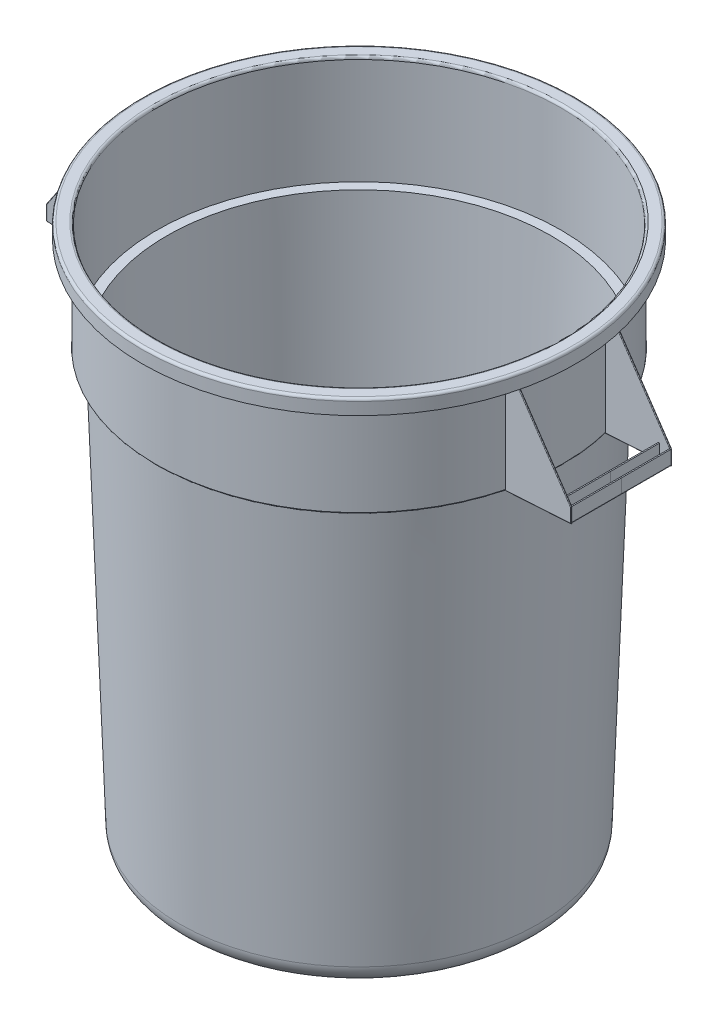
SolidWorks part; units mm, degrees
ref_plane "Front Plane" through (0, 0, 0) normal (0, 0, 1) x (1, 0, 0)
ref_plane "Top Plane" through (0, 0, 0) normal (0, 1, 0) x (1, 0, 0)
ref_plane "Center Plane" through (0, 0, 0) normal (1, 0, 0) x (0, 0, -1)
sketch "Sketch1" plane through (0, 0, 0) normal (0, 0, 1) x (1, 0, 0)
  line L0 (-158.75, 0) -> (-228.6, 0)
  line L1 (-228.6, 0) -> (-247.892, 552.45)
  line L2 (-260.592, 692.15) -> (-279.642, 692.15)
  line L3 (-279.642, 692.15) -> (-279.642, 673.1)
  line L4 (-158.75, 0) -> (-158.75, 34.925)
  line L5 (0, 0) -> (0, 802.8221) construction
  line L6 (-158.75, 34.925) -> (0, 34.925)
  line L7 (-247.892, 552.45) -> (-260.592, 552.45)
  line L8 (-260.592, 552.45) -> (-260.592, 692.15)
  line L9 (-157.1625, 33.3375) -> (0, 33.3375)
  line L10 (-157.1625, -1.5875) -> (-157.1625, 33.3375)
  line L11 (-157.1625, -1.5875) -> (-230.133, -1.5875)
  line L12 (-230.133, -1.5875) -> (-249.425, 550.8625)
  line L13 (-249.425, 550.8625) -> (-262.1795, 550.8625)
  line L14 (-262.1795, 550.8625) -> (-262.1795, 690.5625)
  line L15 (-262.1795, 690.5625) -> (-278.0545, 690.5625)
  line L16 (-278.0545, 690.5625) -> (-278.0545, 673.1)
  line L17 (-279.642, 673.1) -> (-278.0545, 673.1)
  line L18 (157.1625, 33.3375) -> (0, 33.3375)
  line L19 (158.75, 34.925) -> (0, 34.925)
  line L20 (279.642, 673.1) -> (278.0545, 673.1)
  line L21 (278.0545, 690.5625) -> (278.0545, 673.1)
  line L22 (262.1795, 690.5625) -> (278.0545, 690.5625)
  line L23 (262.1795, 550.8625) -> (262.1795, 690.5625)
  line L24 (249.425, 550.8625) -> (262.1795, 550.8625)
  line L25 (230.133, -1.5875) -> (249.425, 550.8625)
  line L26 (157.1625, -1.5875) -> (230.133, -1.5875)
  line L27 (157.1625, -1.5875) -> (157.1625, 33.3375)
  line L28 (260.592, 552.45) -> (260.592, 692.15)
  line L29 (247.892, 552.45) -> (260.592, 552.45)
  line L30 (158.75, 0) -> (158.75, 34.925)
  line L31 (279.642, 692.15) -> (279.642, 673.1)
  line L32 (260.592, 692.15) -> (279.642, 692.15)
  line L33 (228.6, 0) -> (247.892, 552.45)
  line L34 (158.75, 0) -> (228.6, 0)
  line L35 (-262.1795, 550.8625) -> (-338.3795, 555.997)
  line L36 (-338.3795, 555.997) -> (-338.3795, 575.047)
  line L37 (-338.3795, 575.047) -> (-279.642, 673.1)
  line L38 (-338.3795, 575.047) -> (-336.792, 575.047)
  line L39 (-336.792, 575.047) -> (-336.792, 557.5845)
  line L40 (-336.792, 557.5845) -> (-324.092, 557.5845)
  line L41 (-324.092, 557.5845) -> (-324.092, 575.047)
  line L42 (-324.092, 575.047) -> (-322.5045, 575.047)
  line L43 (-322.5045, 575.047) -> (-322.5045, 555.997)
  line L44 (-322.5045, 555.997) -> (-338.3795, 555.997)
  dimension "D2" = 692.15
  dimension "D3" = 19.05
  dimension "D4" = 92
  dimension "D5" = 19.05
  dimension "D6" = 69.85
  dimension "D7" = 34.925
  dimension "D8" = 12.7
  dimension "D9" = 139.7
  dimension "D11" = 76.2
  dimension "D12" = 114.3
  dimension "D13" = 19.05
  dimension "D14" = 1.5875
  dimension "D15" = 1.5875
  dimension "D16" = 1.5875
  dimension "D17" = 12.7
  dimension "D18" = 457.2
  dimension "D19" = 557.6965
  dimension "D10" = 1.5875
sketch "Sketch2" plane through (0, 0, 0) normal (0, 0, 1) x (1, 0, 0)
  line L0 (-279.642, 673.1) -> (-278.0545, 673.1) construction
  line L1 (-278.0545, 690.5625) -> (-278.0545, 673.1) construction
  line L2 (-279.642, 692.15) -> (-279.642, 673.1) construction
  line L3 (-262.1795, 690.5625) -> (-278.0545, 690.5625) construction
  line L4 (-260.592, 692.15) -> (-279.642, 692.15) construction
  line L5 (-260.592, 552.45) -> (-260.592, 692.15) construction
  line L6 (-262.1795, 550.8625) -> (-262.1795, 690.5625) construction
  line L7 (-249.425, 550.8625) -> (-262.1795, 550.8625) construction
  line L8 (-247.892, 552.45) -> (-260.592, 552.45) construction
  line L9 (-228.6, 0) -> (-247.892, 552.45) construction
  line L10 (-230.133, -1.5875) -> (-249.425, 550.8625) construction
  line L11 (-157.1625, -1.5875) -> (-230.133, -1.5875) construction
  line L12 (-158.75, 0) -> (-228.6, 0) construction
  line L13 (-158.75, 0) -> (-158.75, 34.925) construction
  line L14 (-157.1625, -1.5875) -> (-157.1625, 33.3375) construction
  line L15 (-158.75, 34.925) -> (0, 34.925) construction
  line L16 (-157.1625, 33.3375) -> (0, 33.3375) construction
  line L17 (-279.642, 673.1) -> (-278.0545, 673.1)
  line L18 (-278.0545, 690.5625) -> (-278.0545, 673.1)
  line L19 (-279.642, 692.15) -> (-279.642, 673.1)
  line L20 (-262.1795, 690.5625) -> (-278.0545, 690.5625)
  line L21 (-260.592, 692.15) -> (-279.642, 692.15)
  line L22 (-260.592, 552.45) -> (-260.592, 692.15)
  line L23 (-262.1795, 550.8625) -> (-262.1795, 690.5625)
  line L24 (-249.425, 550.8625) -> (-262.1795, 550.8625)
  line L25 (-247.892, 552.45) -> (-260.592, 552.45)
  line L26 (-228.6, 0) -> (-247.892, 552.45)
  line L27 (-230.133, -1.5875) -> (-249.425, 550.8625)
  line L28 (-157.1625, -1.5875) -> (-230.133, -1.5875)
  line L29 (-158.75, 0) -> (-228.6, 0)
  line L30 (-158.75, 0) -> (-158.75, 34.925)
  line L31 (-157.1625, -1.5875) -> (-157.1625, 33.3375)
  line L32 (-158.75, 34.925) -> (0, 34.925)
  line L33 (-157.1625, 33.3375) -> (0, 33.3375)
  line L34 (0, 34.925) -> (0, 33.3375)
revolve "Revolve2" add sketch "Sketch2" angle 360 about L5
fillet "Fillet3" radius 3.175 8 edges at (0, 692.15, -260.592) (0, 692.15, -279.642) (0, 690.5625, -278.0545) (0, 690.5625, -262.1795) (0, 0, -158.75) (0, 34.925, -158.75) (0, 33.3375, -157.1625) (0, -1.5875, -157.1625)
fillet "Fillet4" radius 25.4 2 edges at (0, -1.5875, -230.133) (0, 0, -228.6)
ref_plane "Plane1" through (0, 0, 63.5) normal (0, 0, 1) x (1, 0, 0)
sketch "Sketch3" plane through (0, 0, 63.5) normal (0, 0, 1) x (1, 0, 0)
  line L3 (-324.092, 557.5845) -> (-324.092, 575.047) construction
  line L4 (-324.092, 575.047) -> (-322.5045, 575.047) construction
  line L5 (-322.5045, 575.047) -> (-322.5045, 555.997) construction
  line L6 (-322.5045, 555.997) -> (-338.3795, 555.997) construction
  line L7 (-336.792, 557.5845) -> (-324.092, 557.5845) construction
  line L8 (-336.792, 575.047) -> (-336.792, 557.5845) construction
  line L9 (-338.3795, 555.997) -> (-338.3795, 575.047) construction
  line L10 (-338.3795, 575.047) -> (-336.792, 575.047) construction
  line L11 (-324.092, 557.5845) -> (-324.092, 575.047)
  line L12 (-324.092, 575.047) -> (-322.5045, 575.047)
  line L13 (-322.5045, 575.047) -> (-322.5045, 555.997)
  line L14 (-322.5045, 555.997) -> (-338.3795, 555.997)
  line L15 (-336.792, 557.5845) -> (-324.092, 557.5845)
  line L16 (-336.792, 575.047) -> (-336.792, 557.5845)
  line L17 (-338.3795, 555.997) -> (-338.3795, 575.047)
  line L18 (-338.3795, 575.047) -> (-336.792, 575.047)
extrude "Boss-Extrude1" add sketch "Sketch3" against normal up to surface (63.5 mm away) separate body up to plane "Front Plane"
sketch "Sketch5" plane through (-338.3795, 0, 0) normal (-1, 0, 0) x (0, 0, 1)
  line L0 (0, 550.8625) -> (63.5, 550.8625) construction
  line L1 (63.5, 550.8625) -> (65.0875, 550.8625)
  line L2 (63.5, 550.8625) -> (63.5, 673.1)
  line L3 (63.5, 673.1) -> (65.0875, 673.1)
  line L4 (65.0875, 550.8625) -> (65.0875, 673.1)
  line L5 (-249.425, 550.8625) -> (249.425, 550.8625) construction
  line L6 (0, 673.1) -> (63.5, 673.1) construction
  line L7 (0, 692.15) -> (0, 673.1) construction
  line L8 (63.5, 575.047) -> (63.5, 555.997) construction
  line L9 (0, 550.8625) -> (0, 690.5625) construction
  dimension "D2" = 1.5875
extrude "Boss-Extrude3" add sketch "Sketch5" against normal up to surface (84.0061 mm away) separate body up to face at (0, 687.3875, 262.1795)
sketch "Sketch6" plane through (0, 0, 65.0875) normal (0, 0, 1) x (1, 0, 0)
  line L0 (-253.9718, 550.8625) -> (-338.3795, 555.997)
  line L1 (-338.3795, 555.997) -> (-338.3795, 550.8625)
  line L2 (-338.3795, 550.8625) -> (-253.9718, 550.8625)
  line L3 (-338.3795, 575.047) -> (-338.3795, 673.1)
  line L4 (-338.3795, 673.1) -> (-271.9619, 673.1)
  line L5 (-271.9619, 673.1) -> (-338.3795, 575.047)
  line L6 (-279.642, 673.1) -> (279.642, 673.1) construction
extrude "Cut-Extrude1" cut sketch "Sketch6" against normal up to surface (1.5875 mm away) up to face at (-296.3764, 611.9813, 63.5)
fillet "Fillet7" radius 1.5875 4 edges at (-336.792, 557.5845, 31.75) (-324.092, 557.5845, 31.75) (-322.5045, 555.997, 31.75) (-338.3795, 555.997, 31.75)
fillet "Fillet11" radius 1.5875 1 edges at (0, 550.8625, -262.1795)
fillet "Fillet12" radius 0.7937 5 edges at (-296.3764, 553.4419, 63.5) (-296.1757, 553.4297, 65.0875) (-305.1707, 624.0735, 63.5) (-305.1707, 624.0735, 65.0875) (-338.3795, 565.522, 65.0875)
mirror "Mirror11" about plane through (0, 0, 0) normal (0, 0, 1) of bodies 108 106
mirror "Mirror12" about plane through (0, 0, 0) normal (1, 0, 0) of bodies 108 106 112 111
sketch "Sketch10" plane through (0, 0, 0) normal (0, 0, 1) x (1, 0, 0)
  text T0 "<b>BRUTE.</b>" font "Swis721 Blk BT" height in points 150
wrap "Wrap1" [suppressed] sketch "Sketch10" source sketch "Sketch10"
sketch "Sketch11" plane through (0, 0, 0) normal (0, 0, 1) x (1, 0, 0)
  line L0 (48.9066, 594.3053) -> (48.9066, 575.4018)
  line L1 (-48.7265, 594.3053) -> (-48.7265, 575.4018)
  line L2 (48.1128, 593.6701) -> (48.1128, 576.0497)
  line L3 (-47.9328, 593.6564) -> (-47.9328, 576.0151)
  line L4 (-48.644, 575.3802) -> (-47.8327, 575.9893)
  line L5 (-48.7265, 575.4018) -> (-47.9328, 576.0151)
  spline S0 degree 3 poles (-48.7265, 594.3053) (-32.7583, 597.5609) (0.0041, 601.6281) (32.8422, 597.9377) (48.9066, 594.3053) knots 0 0 0 0 0.497603 1 1 1 1
  spline S1 degree 3 poles (-48.644, 575.3802) (-42.3882, 573.7414) (-26.3592, 570.5267) (6.5271, 568.4947) (32.784, 572.0981) (48.9066, 575.4018) knots 0.000866 0.000866 0.000866 0.000866 0.197761 0.498006 1 1 1 1
  spline S4 degree 3 poles (-47.9328, 593.6564) (-32.1407, 596.8418) (-7.9532, 599.796) (24.3071, 598.079) (40.2463, 595.4252) (48.1128, 593.6701) knots 0.006613 0.006613 0.006613 0.006613 0.500071 0.7468 0.993529 0.993529 0.993529 0.993529
  spline S5 degree 3 poles (48.1128, 576.0497) (40.1953, 574.4383) (24.2366, 571.743) (0.0438, 569.9504) (-24.1758, 571.096) (-40.0599, 573.9826) (-47.8327, 575.9893) knots 0.006239 0.006239 0.006239 0.006239 0.253031 0.499822 0.746614 0.992351 0.992351 0.992351 0.992351
  dimension "D1" = 18.9035
  dimension "D2" = 97.6331
  dimension "D3" = 26.6544
  dimension "D4" = 30.0495
  dimension "D5" = 26.0563
  dimension "D6" = 22.5767
  dimension "D7" = 49.0408
  dimension "D8" = 78.1962
sketch "Sketch13" plane through (0, 0, 0) normal (0, 0, 1) x (1, 0, 0)
  text T0 "Commercial Products" font "Century Gothic" height 6.35
sketch "Sketch14" plane through (0, 0, 0) normal (0, 0, 1) x (1, 0, 0)
  text T0 "Rubbermaid" font "Century Gothic" height 9.525
wrap "Wrap5" [suppressed] sketch "Sketch13" source sketch "Sketch13"
wrap "Wrap6" [suppressed] sketch "Sketch14" source sketch "Sketch14"
wrap "Wrap7" [suppressed] sketch "Sketch11" source sketch "Sketch11"
pattern_linear "LPattern1" [suppressed] count 2 spacing 139.7 along (0, 1, 0) of bodies 113 114 115 116 106 112 111 108 105
ref_plane "Plane2" through (0, 428.625, 0) normal (0, 1, 0) x (1, 0, 0)
equation "\"Weight(KG)\"=\"Weight\"*0.453"
